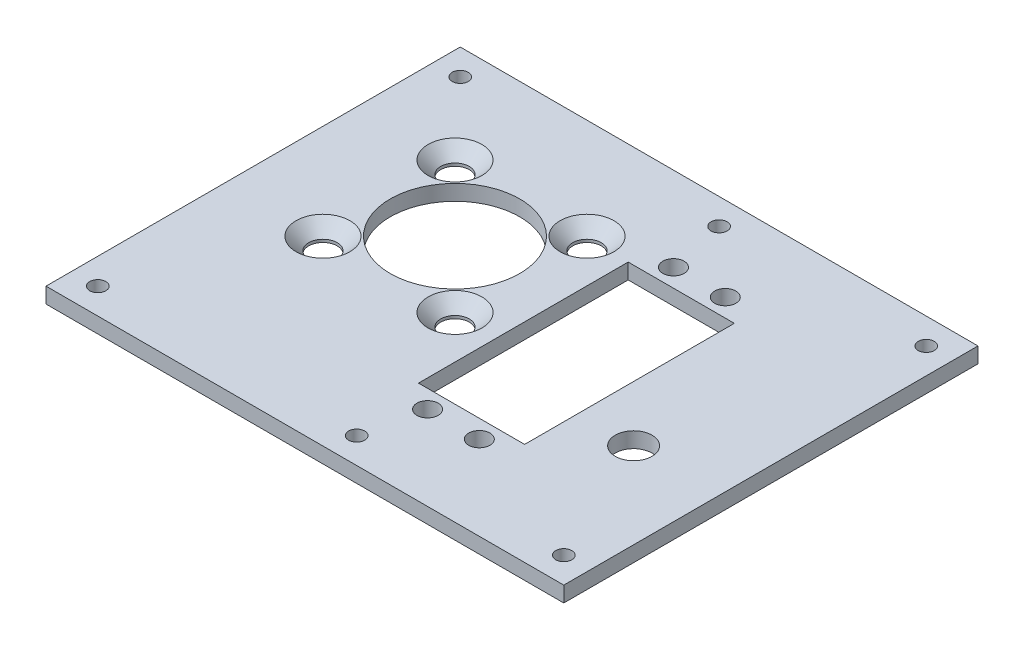
SolidWorks part; units mm, degrees
ref_plane "Płaszczyzna przednia" through (0, 0, 0) normal (0, 0, 1) x (1, 0, 0)
ref_plane "Płaszczyzna górna" through (0, 0, 0) normal (0, 1, 0) x (1, 0, 0)
ref_plane "Płaszczyzna prawa" through (0, 0, 0) normal (1, 0, 0) x (0, 0, -1)
sketch "Szkic1" plane through (0, 0, 0) normal (0, 1, 0) x (1, 0, 0)
  line L6 (-20.2688, 11.7569) -> (5.2312, -13.7431) construction
  line L11 (-38.6633, 31.161) -> (61.3367, 31.161)
  line L12 (-38.6633, 31.161) -> (-38.6633, -48.839)
  line L13 (-38.6633, -48.839) -> (61.3367, -48.839)
  line L14 (61.3367, 31.161) -> (61.3367, -48.839)
  line L15 (-20.2688, -13.7431) -> (5.2312, 11.7569) construction
  line L17 (13.5251, 11.411) -> (34.0251, 11.411)
  line L18 (13.5251, 11.411) -> (13.5251, -29.089)
  line L23 (13.5251, -29.089) -> (34.0251, -29.089)
  line L24 (34.0251, 11.411) -> (34.0251, -29.089)
  circle A0 centre (-7.5188, -0.9931) radius 12.5
  circle A2 centre (-20.2688, 11.7569) radius 2.55
  circle A3 centre (5.2312, 11.7569) radius 2.55
  circle A4 centre (5.2312, -13.7431) radius 2.55
  circle A5 centre (-20.2688, -13.7431) radius 2.55
  circle A6 centre (18.7751, 14.911) radius 2.05
  circle A7 centre (28.7751, 14.911) radius 2.05
  circle A8 centre (18.7751, -32.589) radius 2.05
  circle A9 centre (28.7751, -32.589) radius 2.05
  circle A10 centre (23.7751, -18.789) radius 0.5
  circle A11 centre (-7.5188, -0.9931) radius 0.5
  circle A12 centre (44.7751, -18.789) radius 3.55
  circle A13 centre (44.7751, -18.789) radius 0.5
  circle A14 centre (-33.6633, 26.161) radius 1.55
  circle A15 centre (56.3367, 26.161) radius 1.55
  circle A16 centre (56.3367, -43.839) radius 1.55
  circle A17 centre (-33.6633, -43.839) radius 1.55
  circle A18 centre (16.3367, 26.161) radius 1.55
  circle A19 centre (16.3367, -43.839) radius 1.55
  point P18 (23.7751, -29.089)
  point P22 (23.7751, 11.411)
  point P27 (11.3367, -8.839)
  dimension "D3" = 10.3
  dimension "D5" = 3.5
  dimension "D13" = 36
  dimension "D18" = 19.75
  dimension "D20" = 5.1
  dimension "D22" = 25
  dimension "D23" = 7.1
  dimension "D24" = 4.1
  dimension "D25" = 47.5
  dimension "D26" = 37.5616
  dimension "D1" = 100
  dimension "D2" = 80
  dimension "D4" = 10.25
  dimension "D6" = 3.5
  dimension "D7" = 5
  dimension "D8" = 5
  dimension "D9" = 3.5
  dimension "D10" = 3.5
  dimension "D11" = 5
  dimension "D12" = 5
  dimension "D14" = 21
  dimension "D15" = 40.5
  dimension "D16" = 20.5
  dimension "D17" = 10.3
  dimension "D19" = 19.75
  dimension "D21" = 25.5
  dimension "D27" = 30.05
extrude "Dodanie-wyciągnięcie1" add sketch "Szkic1" along normal blind 3 contours L14 L11 L12 L13 A12 A9 A8 A7 A6 A5 A4 A3 A2 A0 L17 L24 L23 L18 region at (11.0911, 0, 9.4735)
sketch "Sketch1" plane through (0, 0, 0) normal (0, 1, 0) x (1, 0, 0)
  point P0 (-20.2688, -13.7431)
  point P3 (5.2312, -13.7431)
  point P6 (5.2312, 11.7569)
  point P9 (-20.2688, 11.7569)
sketch "Sketch3" plane through (0, 3, 0) normal (0, 1, 0) x (1, 0, 0)
  point P0 (-20.2688, -13.7431)
  point P3 (5.2312, -13.7431)
  point P6 (5.2312, 11.7569)
  point P9 (-20.2688, 11.7569)
hole_wizard "CSK for M5 Countersunk Flat Head Screw2" positions "Sketch3" profile "Sketch4" countersink size "M5" standard "ISO" end condition through all
sketch "Sketch4" plane through (-20.2688, 3, 13.7431) normal (1, 0, 0) x (0, 0, 1)
  line L0 (0, 0) -> (0, 3)
  line L1 (0, 3) -> (2.75, 3)
  line L2 (2.75, 3) -> (2.75, 2.45)
  line L3 (2.75, 2.45) -> (5.2, 0)
  line L5 (5.2, 0) -> (0, 0)
  line L6 (-2.75, 2.45) -> (-5.2, 0) construction
  line L11 (0, -6.35) -> (0, 107.95) construction
  dimension "Thru Hole Dia." = 5.5
  dimension "Thru Hole Depth" = 3
  dimension "Near C'Sink Dia." = 10.4
  dimension "Near C'Sink Angle" = 90
